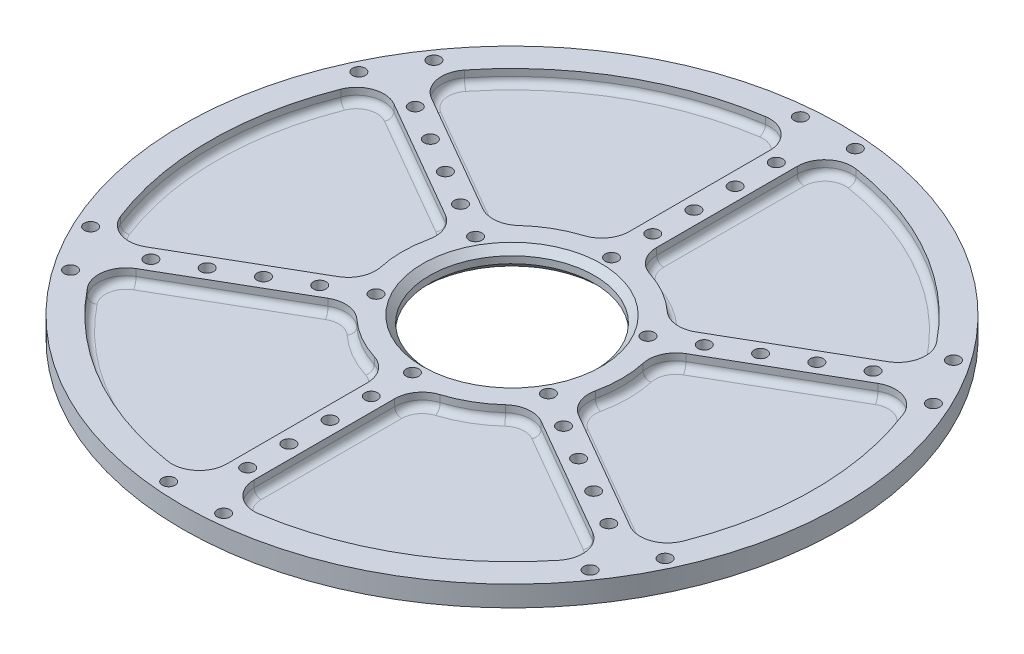
SolidWorks part; units mm, degrees
material "6061 Alloy"
ref_plane "Front Plane" through (0, 0, 0) normal (0, 0, 1) x (1, 0, 0)
ref_plane "Top Plane" through (0, 0, 0) normal (0, 1, 0) x (1, 0, 0)
ref_plane "Right Plane" through (0, 0, 0) normal (1, 0, 0) x (0, 0, -1)
sketch "Sketch1" plane through (0, 0, 0) normal (0, 1, 0) x (1, 0, 0)
  circle A0 centre (0, 0) radius 76.2
  dimension "D1" = 152.4
extrude "Boss-Extrude1" add sketch "Sketch1" along normal blind 4.7625
sketch "Sketch9" plane through (0, 4.7625, -4.7625) normal (0, -1, 0) x (1, 0, 0)
  line L0 (0, 4.7625) -> (0, 81.5614) construction
  line L1 (3.175, 67.5441) -> (3.175, 35.0501)
  line L2 (-3.175, 67.5441) -> (-3.175, 35.0501)
  line L3 (52.7829, 38.9029) -> (24.6423, 22.6559)
  line L4 (55.9579, 33.4036) -> (27.8173, 17.1567)
  line L5 (55.9579, -23.8786) -> (27.8173, -7.6317)
  line L6 (52.7829, -29.3779) -> (24.6423, -13.1309)
  line L7 (3.175, -58.0191) -> (3.175, -25.5251)
  line L8 (-3.175, -58.0191) -> (-3.175, -25.5251)
  line L9 (-52.7829, -29.3779) -> (-24.6423, -13.1309)
  line L10 (-55.9579, -23.8786) -> (-27.8173, -7.6317)
  line L11 (-55.9579, 33.4036) -> (-27.8173, 17.1567)
  line L12 (-52.7829, 38.9029) -> (-24.6423, 22.6559)
  line L13 (-34.925, 65.2544) -> (-38.1, 70.7536) construction
  circle A1 centre (0, 4.7625) radius 76.2 construction
  arc A2 (-10.4775, 73.8222) -> (-54.5687, 48.3661) centre (0, 4.7625) ccw
  arc A3 (-7.62, 28.9926) -> (-17.1738, 23.4766) centre (0, 4.7625) ccw
  circle A4 centre (0, 4.7625) radius 19.05
  circle A5 centre (0, 4.7625) radius 69.85 construction
  circle A6 centre (0, 4.7625) radius 25.4 construction
  arc A7 (-7.62, 28.9926) -> (-3.175, 35.0501) centre (-9.525, 35.0501) ccw
  arc A8 (-10.4775, 73.8222) -> (-3.175, 67.5441) centre (-9.525, 67.5441) cw
  arc A9 (7.62, 28.9926) -> (3.175, 35.0501) centre (9.525, 35.0501) cw
  arc A10 (10.4775, 73.8222) -> (3.175, 67.5441) centre (9.525, 67.5441) ccw
  arc A11 (54.5687, 48.3661) -> (52.7829, 38.9029) centre (49.6079, 44.4022) cw
  arc A12 (17.1738, 23.4766) -> (24.6423, 22.6559) centre (21.4673, 28.1552) ccw
  arc A13 (24.7938, 10.2784) -> (27.8173, 17.1567) centre (30.9923, 11.6574) cw
  arc A14 (65.0462, 30.2186) -> (55.9579, 33.4036) centre (59.1329, 27.9044) ccw
  arc A15 (65.0462, -20.6936) -> (55.9579, -23.8786) centre (59.1329, -18.3794) cw
  arc A16 (24.7938, -0.7534) -> (27.8173, -7.6317) centre (30.9923, -2.1324) ccw
  arc A17 (17.1738, -13.9516) -> (24.6423, -13.1309) centre (21.4673, -18.6302) cw
  arc A18 (54.5687, -38.8411) -> (52.7829, -29.3779) centre (49.6079, -34.8772) ccw
  arc A19 (10.4775, -64.2972) -> (3.175, -58.0191) centre (9.525, -58.0191) cw
  arc A20 (7.62, -19.4676) -> (3.175, -25.5251) centre (9.525, -25.5251) ccw
  arc A21 (-7.62, -19.4676) -> (-3.175, -25.5251) centre (-9.525, -25.5251) cw
  arc A22 (-10.4775, -64.2972) -> (-3.175, -58.0191) centre (-9.525, -58.0191) ccw
  arc A23 (-54.5687, -38.8411) -> (-52.7829, -29.3779) centre (-49.6079, -34.8772) cw
  arc A24 (-17.1738, -13.9516) -> (-24.6423, -13.1309) centre (-21.4673, -18.6302) ccw
  arc A25 (-24.7938, -0.7534) -> (-27.8173, -7.6317) centre (-30.9923, -2.1324) cw
  arc A26 (-65.0462, -20.6936) -> (-55.9579, -23.8786) centre (-59.1329, -18.3794) ccw
  arc A27 (-65.0462, 30.2186) -> (-55.9579, 33.4036) centre (-59.1329, 27.9044) cw
  arc A28 (-24.7938, 10.2784) -> (-27.8173, 17.1567) centre (-30.9923, 11.6574) ccw
  arc A29 (-17.1738, 23.4766) -> (-24.6423, 22.6559) centre (-21.4673, 28.1552) cw
  arc A30 (-54.5687, 48.3661) -> (-52.7829, 38.9029) centre (-49.6079, 44.4022) ccw
  arc A31 (-65.0462, 30.2186) -> (-65.0462, -20.6936) centre (0, 4.7625) ccw
  arc A32 (-24.7938, 10.2784) -> (-24.7938, -0.7534) centre (0, 4.7625) ccw
  arc A33 (-17.1738, -13.9516) -> (-7.62, -19.4676) centre (0, 4.7625) ccw
  arc A34 (-54.5687, -38.8411) -> (-10.4775, -64.2972) centre (0, 4.7625) ccw
  arc A35 (7.62, -19.4676) -> (17.1738, -13.9516) centre (0, 4.7625) ccw
  arc A36 (10.4775, -64.2972) -> (54.5687, -38.8411) centre (0, 4.7625) ccw
  arc A37 (65.0462, -20.6936) -> (65.0462, 30.2186) centre (0, 4.7625) ccw
  arc A38 (24.7938, -0.7534) -> (24.7938, 10.2784) centre (0, 4.7625) ccw
  arc A39 (17.1738, 23.4766) -> (7.62, 28.9926) centre (0, 4.7625) ccw
  arc A40 (54.5687, 48.3661) -> (10.4775, 73.8222) centre (0, 4.7625) ccw
  circle A41 centre (0, 4.7625) radius 76.2 construction
  point P15 (-3.175, 29.9633)
  point P18 (-3.175, 74.5403)
  point P21 (3.175, 29.9633)
  point P24 (3.175, 74.5403)
  point P26 (-34.3533, 64.2641)
  point P88 (0, 4.7625)
  dimension "D2" = 50.8
  dimension "D3" = 6.35
  dimension "D5" = 6.35
  dimension "D1" = 6.35
  dimension "D4" = 6.35
  dimension "D6" = 6
extrude "Cut-Extrude6" cut sketch "Sketch9" along normal blind 3.175
fillet "Fillet1" radius 1.5875 48 edges at (-3.175, 1.5875, 46.5346) (-5.3853, 1.5875, 67.5967) (-34.925, 1.5875, 60.4919) (-55.8478, 1.5875, 38.4622) (-38.7126, 1.5875, 26.0169) (-20.7737, 1.5875, 17.0807) (-12.7, 1.5875, 21.997) (-4.4055, 1.5875, 26.5309) (20.7737, 1.5875, 17.0807) (38.7126, 1.5875, 26.0169) (55.8478, 1.5875, 38.4622) (34.925, 1.5875, 60.4919) (5.3853, 1.5875, 67.5967) (3.175, 1.5875, 46.5346) (4.4055, 1.5875, 26.5309) (12.7, 1.5875, 21.997) (25.1791, 1.5875, -9.4502) (41.8876, 1.5875, -20.5177) (61.2331, 1.5875, -29.1345) (69.85, 1.5875, 0) (61.2331, 1.5875, 29.1345) (41.8876, 1.5875, 20.5177) (25.1791, 1.5875, 9.4502) (25.4, 1.5875, 0) (4.4055, 1.5875, -26.5309) (3.175, 1.5875, -46.5346) (5.3853, 1.5875, -67.5967) (34.925, 1.5875, -60.4919) (55.8478, 1.5875, -38.4622) (38.7126, 1.5875, -26.0169) (20.7737, 1.5875, -17.0807) (12.7, 1.5875, -21.997) (-20.7737, 1.5875, -17.0807) (-38.7126, 1.5875, -26.0169) (-55.8478, 1.5875, -38.4622) (-34.925, 1.5875, -60.4919) (-5.3853, 1.5875, -67.5967) (-3.175, 1.5875, -46.5346) (-4.4055, 1.5875, -26.5309) (-12.7, 1.5875, -21.997) (-25.1791, 1.5875, 9.4502) (-41.8876, 1.5875, 20.5177) (-61.2331, 1.5875, 29.1345) (-69.85, 1.5875, 0) (-61.2331, 1.5875, -29.1345) (-41.8876, 1.5875, -20.5177) (-25.1791, 1.5875, -9.4502) (-25.4, 1.5875, 0)
sketch "Sketch10" plane through (0, 1.5875, 0) normal (0, 1, 0) x (1, 0, 0)
  circle A1 centre (0, 0) radius 19.05
  circle A2 centre (0, 0) radius 19.05
  dimension "D1" = 0
extrude "Cut-Extrude7" cut sketch "Sketch10" against normal through all
chamfer "Chamfer1" distance 1.5875 angle 45 2 edges at (0, 0, 19.05) (0, 4.7625, -19.05)
hole_wizard "#4 Clearance Hole1" positions "Sketch11" profile "Sketch12" hole size "#4" standard "ANSI Inch"
sketch "Sketch11" plane through (0, 4.7625, 0) normal (0, 1, 0) x (1, 0, 0)
  line L0 (-12.7, -21.997) -> (-10.3187, -17.8726) construction
  line L2 (0, -23.0188) -> (0, -38.1554) construction
  circle A0 centre (0, 0) radius 23.0188 construction
  arc A1 (-17.1738, -18.7141) -> (-7.62, -24.2301) centre (0, 0) ccw construction
  circle A2 centre (0, 0) radius 20.6375 construction
  point P0 (0, -23.0188)
  point P17 (-11.5094, -19.9348)
sketch "Sketch12" plane through (0, 4.7625, 23.0188) normal (1, 0, 0) x (0, 0, 1)
  line L0 (0, 0) -> (0, 26.2852)
  line L1 (0, 26.2852) -> (1.4732, 25.4)
  line L2 (1.4732, 25.4) -> (1.4732, 0)
  line L5 (1.4732, 0) -> (0, 0)
  line L10 (0, 26.2852) -> (-1.4732, 25.4) construction
  line L11 (0, -6.35) -> (0, 107.95) construction
  dimension "Hole Dia." = 2.9464
  dimension "Hole Depth" = 25.4
  dimension "Drill Angle" = 118
hole_wizard "#4 Clearance Hole2" positions "Sketch13" profile "Sketch14" hole size "#4" standard "ANSI Inch"
sketch "Sketch13" plane through (0, 4.7625, 0) normal (0, 1, 0) x (1, 0, 0)
  line L0 (0, -76.2) -> (0, -69.85) construction
  circle A0 centre (0, 0) radius 76.2 construction
  arc A1 (14.3383, -71.6035) -> (-14.3383, -71.6035) centre (0, 0) cw construction
  arc A2 (-54.5687, -43.6036) -> (-10.4775, -69.0597) centre (0, 0) ccw construction
  point P0 (6.35, -73.025)
  point P11 (-6.35, -73.025)
  point P27 (0, 0)
  point P31 (0, -73.025)
  point P32 (0, -73.025)
  point P33 (-14.3383, -71.6035)
  dimension "D1" = 3.175
  dimension "D2" = 12.7
sketch "Sketch14" plane through (6.35, 4.7625, 73.025) normal (1, 0, 0) x (0, 0, 1)
  line L0 (0, 0) -> (0, 26.2852)
  line L1 (0, 26.2852) -> (1.4732, 25.4)
  line L2 (1.4732, 25.4) -> (1.4732, 0)
  line L5 (1.4732, 0) -> (0, 0)
  line L10 (0, 26.2852) -> (-1.4732, 25.4) construction
  line L11 (0, -6.35) -> (0, 107.95) construction
  dimension "Hole Dia." = 2.9464
  dimension "Hole Depth" = 25.4
  dimension "Drill Angle" = 118
hole_wizard "#4 Clearance Hole3" positions "Sketch15" profile "Sketch16" hole size "#4" standard "ANSI Inch"
sketch "Sketch15" plane through (0, 4.7625, 0) normal (0, 1, 0) x (1, 0, 0)
  line L2 (-3.175, -46.5346) -> (3.175, -46.5346) construction
  line L3 (-3.175, -30.2876) -> (-3.175, -62.7816) construction
  line L4 (3.175, -62.7816) -> (3.175, -30.2876) construction
  line L6 (0, -42.0687) -> (0, -32.5437) construction
  line L8 (0, -32.5437) -> (0, -23.0188) construction
  point P2 (0, -32.5437)
  point P23 (0, -46.5346)
  point P33 (0, -42.0687)
  point P34 (0, -51.5937)
  point P35 (0, -61.1187)
  dimension "D1" = 4
  dimension "D3" = 9.525
sketch "Sketch16" plane through (0, 4.7625, 32.5437) normal (1, 0, 0) x (0, 0, 1)
  line L0 (0, 0) -> (0, 26.2852)
  line L1 (0, 26.2852) -> (1.4732, 25.4)
  line L2 (1.4732, 25.4) -> (1.4732, 0)
  line L5 (1.4732, 0) -> (0, 0)
  line L10 (0, 26.2852) -> (-1.4732, 25.4) construction
  line L11 (0, -6.35) -> (0, 107.95) construction
  dimension "Hole Dia." = 2.9464
  dimension "Hole Depth" = 25.4
  dimension "Drill Angle" = 118
pattern_circular "CirPattern1" count 6 over 360 about axis through (0, 4.7625, 0) along (0, -1, 0) of "#4 Clearance Hole1", "#4 Clearance Hole2", "#4 Clearance Hole3"
